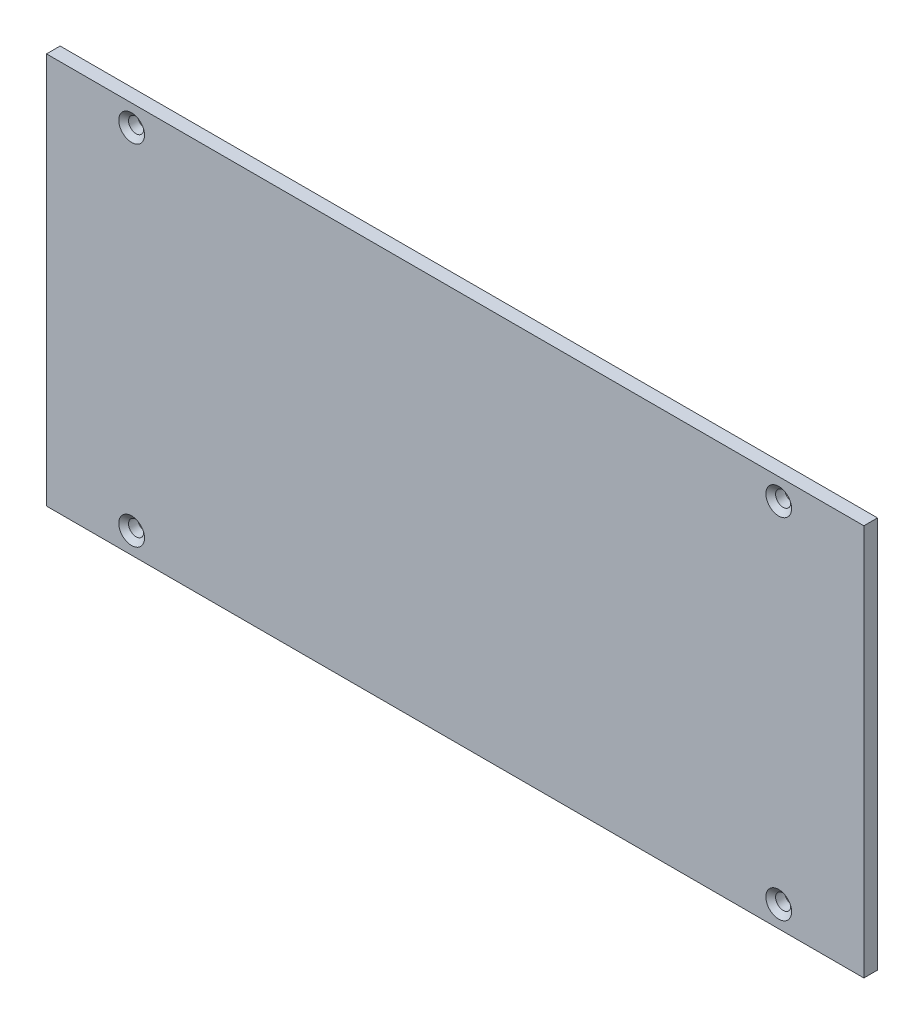
SolidWorks part; units mm, degrees
material "6061-T4 (SS)"
ref_plane "Front Plane" through (0, 0, 0) normal (0, 0, 1) x (1, 0, 0)
ref_plane "Top Plane" through (0, 0, 0) normal (0, 1, 0) x (1, 0, 0)
ref_plane "Right Plane" through (0, 0, 0) normal (1, 0, 0) x (0, 0, -1)
sketch "Sketch1" plane through (0, 0, 0) normal (0, 0, 1) x (1, 0, 0)
  line L1 (0, 0) -> (96, 0)
  line L2 (0, 0) -> (0, 46)
  line L3 (0, 46) -> (96, 46)
  line L4 (96, 0) -> (96, 46)
  dimension "D1" = 46
  dimension "D2" = 96
extrude "Boss-Extrude1" add sketch "Sketch1" along normal blind 1.6002
sketch "Sketch2" plane through (0, 0, 1.6002) normal (0, 0, 1) x (1, 0, 0)
  circle A0 centre (75.2, 23.05) radius 13.1445
  circle A1 centre (75.2, 23.05) radius 13.1445 construction
extrude "Cut-Extrude1" [suppressed] cut sketch "Sketch2" against normal through all
hole_wizard "CSK for #0 Flat Head Machine Screw (100)1" positions "Sketch6" profile "Sketch7" countersink size "#0" standard "ANSI Inch" end condition through all
sketch "Sketch6" plane through (0, 0, 1.6002) normal (0, 0, 1) x (1, 0, 0)
  line L0 (0, 46) -> (0, 0) construction
  line L1 (10, 43.5) -> (10, 2.5) construction
  line L2 (10, 2.5) -> (86, 2.5) construction
  line L3 (86, 2.5) -> (86, 43.5) construction
  line L4 (86, 43.5) -> (10, 43.5) construction
  line L6 (96, 0) -> (96, 46) construction
  line L8 (96, 46) -> (0, 46) construction
  line L9 (0, 0) -> (96, 0) construction
  point P0 (10, 43.5)
  point P2 (10, 2.5)
  point P4 (86, 2.5)
  point P6 (86, 43.5)
  dimension "D1" = 10
  dimension "D2" = 10
  dimension "D3" = 2.5
  dimension "D4" = 2.5
sketch "Sketch7" plane through (10, 43.5, 1.6002) normal (1, 0, 0) x (0, -1, 0)
  line L0 (0, 0) -> (0, 1.6002)
  line L1 (0, 1.6002) -> (0.889, 1.6002)
  line L2 (0.889, 1.6002) -> (0.889, 0.5222)
  line L3 (0.889, 0.5222) -> (1.5113, 0)
  line L5 (1.5113, 0) -> (0, 0)
  line L6 (-0.889, 0.5222) -> (-1.5113, 0) construction
  line L11 (0, -6.35) -> (0, 107.95) construction
  dimension "Thru Hole Dia." = 1.778
  dimension "Thru Hole Depth" = 1.6002
  dimension "Near C'Sink Dia." = 3.0226
  dimension "Near C'Sink Angle" = 100
